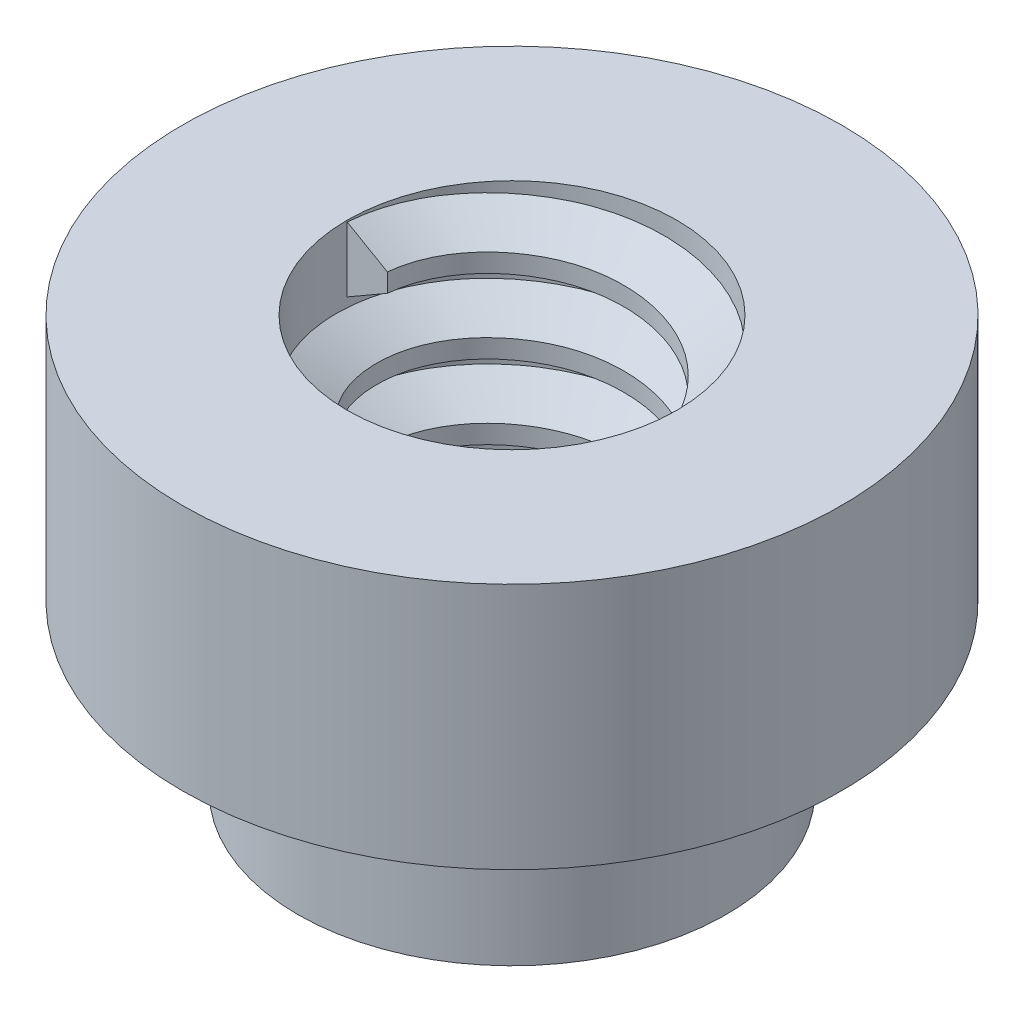
SolidWorks part; units mm, degrees
material "Brass"
ref_plane "Front Plane" through (0, 0, 0) normal (0, 0, 1) x (1, 0, 0)
ref_plane "Top Plane" through (0, 0, 0) normal (0, 1, 0) x (1, 0, 0)
ref_plane "Right Plane" through (0, 0, 0) normal (1, 0, 0) x (0, 0, -1)
ref_axis "CentralAxis" through (0, 1.4241, 0) along (0, -1, 0)
sketch "BaseS" plane through (0, 0, 0) normal (0, 1, 0) x (1, 0, 0)
  circle A0 centre (0, 0) radius 2
  circle A1 centre (0, 0) radius 1
  dimension "Diameter" = 4
  dimension "ThreadDiameter" = 2
extrude "Base" add sketch "BaseS" along normal mid plane 2.5
thread "Thread1" pitch 0.45 start angle 0, offset 0.01, length 0, pitch 0.45, diameter 2
ref_plane "Plane1" through (-1, 1.24, 0) normal (0, 0, 1) x (-1, 0, 0)
sketch "Thread Profile1" plane through (-1, 1.24, 0) normal (0, 0, 1) x (-1, 0, 0)
  line L0 (0, 0) -> (0, 0.45) construction
  line L11 (0, 0) -> (0, 0.3937)
  line L12 (0, 0.3937) -> (-0.2436, 0.2531)
  line L13 (-0.2436, 0.2531) -> (-0.2436, 0.1406)
  line L15 (-0.2436, 0.1406) -> (0, 0)
  line L17 (-0.2436, 0.1969) -> (0, 0.1969) construction
  point P2 (0, 0)
  dimension "Pitch" = 0.45
  dimension "Profile_Angle" = 60
  dimension "Profile_Land" = 0.1125
  dimension "Profile_Height" = 0.2436
sketch "Sketch1" plane through (0, 0, 0) normal (0, 0, 1) x (1, 0, 0)
  line L0 (0, 1.4241) -> (0, -1.3773) construction
  line L1 (2, -1.25) -> (1.3, -1.25)
  line L2 (2, -1.25) -> (2, -0.25)
  line L3 (2, -0.25) -> (1.3, -0.25)
  line L4 (1.3, -1.25) -> (1.3, -0.25)
  point P4 (2, -1.25)
  point P6 (2, -0.7849)
  point P7 (1.4107, -0.7756)
  dimension "D1" = 1.3
  dimension "D2" = 1
revolve "Cut-Revolve1" cut sketch "Sketch1" angle 360 about axis through (0, 1.4241, 0) along (0, -1, 0)
